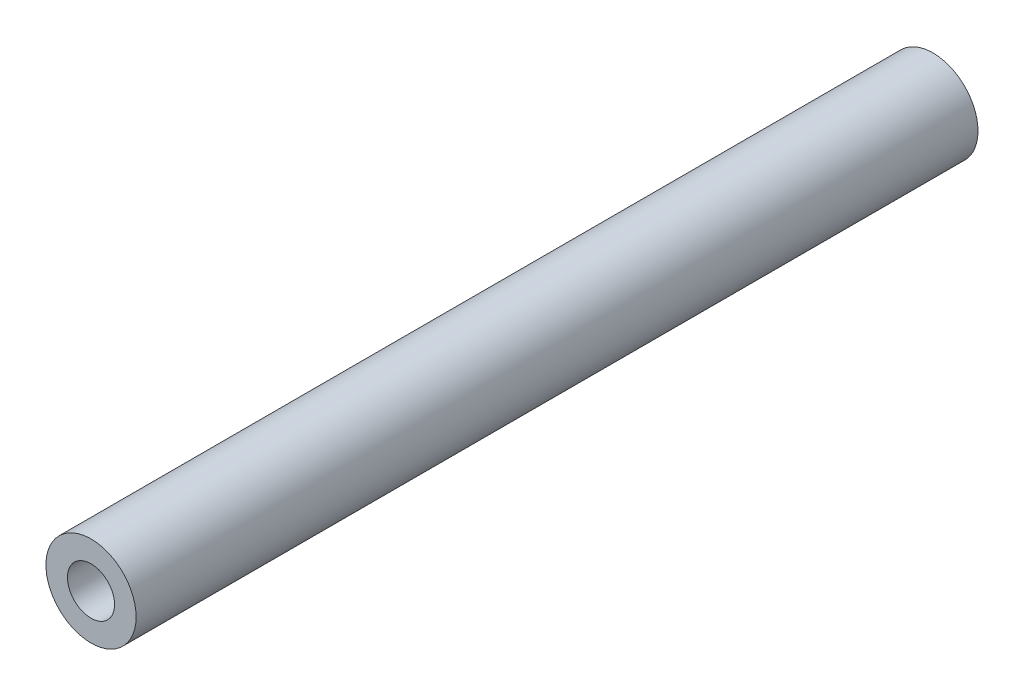
SolidWorks part; units mm, degrees
material "6061-T6 (SS)"
ref_plane "Front Plane" through (0, 0, 0) normal (0, 0, 1) x (1, 0, 0)
ref_plane "Top Plane" through (0, 0, 0) normal (0, 1, 0) x (1, 0, 0)
ref_plane "Right Plane" through (0, 0, 0) normal (1, 0, 0) x (0, 0, -1)
sketch "Sketch1" plane through (0, 0, 0) normal (0, 0, 1) x (1, 0, 0)
  circle A0 centre (0, 0) radius 4.7625
  circle A1 centre (0, 0) radius 2.4892
  dimension "D1" = 4.9784
  dimension "D2" = 9.525
extrude "Boss-Extrude1" add sketch "Sketch1" along normal blind 88.9
